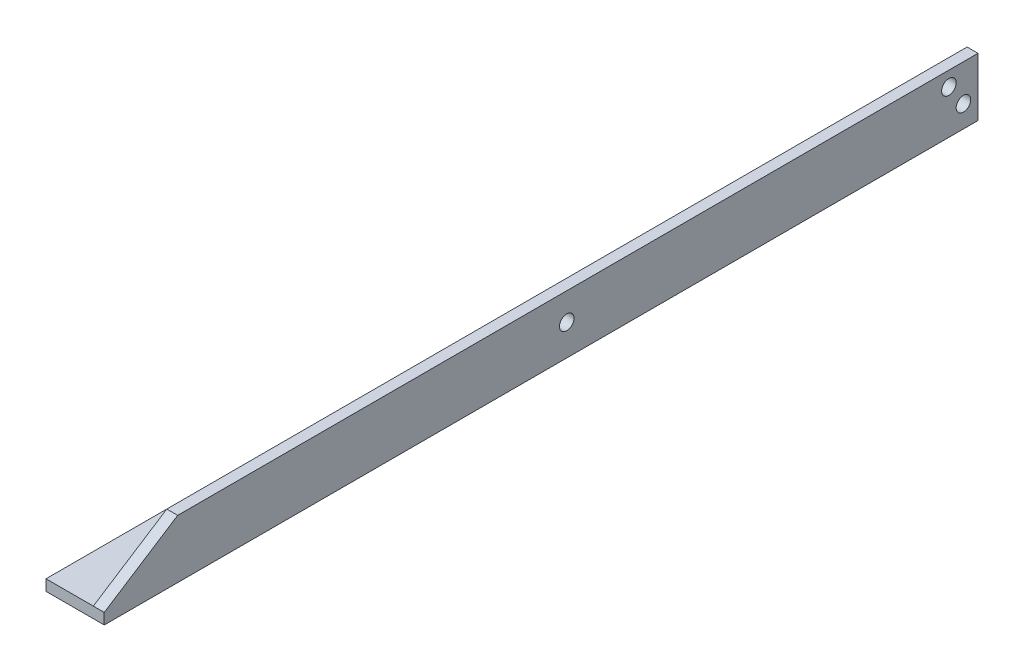
SolidWorks part; units mm, degrees
material "6061 Alloy"
ref_plane "Front Plane" through (0, 0, 0) normal (0, 0, 1) x (1, 0, 0)
ref_plane "Top Plane" through (0, 0, 0) normal (0, 1, 0) x (1, 0, 0)
ref_plane "Right Plane" through (0, 0, 0) normal (1, 0, 0) x (0, 0, -1)
sketch "Sketch1" plane through (0, 0, 0) normal (0, 0, 1) x (1, 0, 0)
  line L0 (0, 0) -> (0, -25.4)
  line L1 (0, -25.4) -> (-25.4, -25.4)
  line L2 (-4.7625, 0) -> (-4.7625, -20.6375)
  line L3 (-4.7625, -20.6375) -> (-25.4, -20.6375)
  line L4 (-4.7625, 0) -> (0, 0)
  line L5 (-25.4, -25.4) -> (-25.4, -20.6375)
  dimension "D1" = 25.4
  dimension "D2" = 25.4
  dimension "D3" = 4.7625
extrude "Boss-Extrude1" add sketch "Sketch1" along normal blind 381
sketch "Sketch4" plane through (-4.7625, 0, 0) normal (-1, 0, 0) x (0, 0, 1)
  line L0 (381, -20.6375) -> (348.9734, 0)
  line L1 (381, 0) -> (0, 0) construction
  dimension "D1" = 38.1
extrude "Cut-Extrude3" cut sketch "Sketch4" against normal through all and the other way through all flip side to cut
sketch "Sketch6" plane through (-4.7625, 0, 0) normal (-1, 0, 0) x (0, 0, 1)
  line L0 (348.9734, 0) -> (0, 0) construction
  line L1 (0, 0) -> (0, -20.6375) construction
  circle A0 centre (6.35, -15.875) radius 3.175
  circle A1 centre (12.7, -6.35) radius 3.175
  dimension "D1" = 6.35
  dimension "D2" = 6.35
  dimension "D3" = 6.35
  dimension "D4" = 6.35
  dimension "D5" = 12.7
  dimension "D6" = 15.875
extrude "Cut-Extrude4" cut sketch "Sketch6" against normal up to next
sketch "Sketch7" plane through (0, 0, 0) normal (1, 0, 0) x (0, 0, -1)
  circle A0 centre (-179.3328, -11.9296) radius 3.175 construction
  circle A1 centre (-179.3328, -11.9296) radius 3.175
extrude "Cut-Extrude5" cut sketch "Sketch7" against normal up to next
sketch "Sketch8" plane through (0, -20.6375, 0) normal (0, 1, 0) x (1, 0, 0)
  line L0 (-25.4, -381) -> (-25.4, 0) construction
  line L1 (-4.7625, 0) -> (-25.4, 0) construction
  circle A0 centre (-15.0812, -12.7) radius 3.175
  dimension "D1" = 6.35
  dimension "D2" = 10.3187
  dimension "D3" = 12.7
extrude "Cut-Extrude6" cut sketch "Sketch8" against normal up to next
equation "\"1..500in\"=1"
